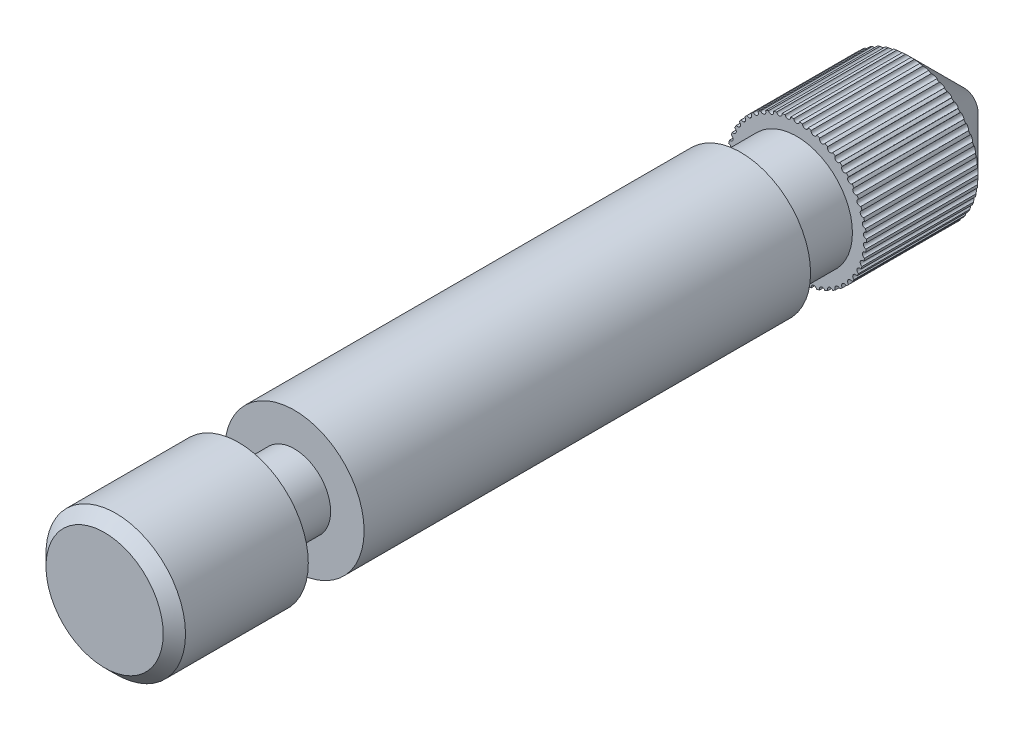
SolidWorks part; units mm, degrees
ref_plane "Front Plane" through (0, 0, 0) normal (0, 0, 1) x (1, 0, 0)
ref_plane "Top Plane" through (0, 0, 0) normal (0, 1, 0) x (1, 0, 0)
ref_plane "Right Plane" through (0, 0, 0) normal (1, 0, 0) x (0, 0, -1)
sketch "Sketch1" plane through (0, 0, 0) normal (0, 0, 1) x (1, 0, 0)
  circle A0 centre (0, 0) radius 1.25
  dimension "D1" = 2.5
extrude "Boss-Extrude1" add sketch "Sketch1" against normal blind 15.4
sketch "Sketch2" plane through (0, 0, 0) normal (1, 0, 0) x (0, 0, -1)
  line L0 (0, 0) -> (15.4, 0) construction
  line L1 (15.4, -1.25) -> (15.4, 1.25) construction
  line L2 (15.4, 1.25) -> (0, 1.25) construction
  line L3 (3.4, 1.25) -> (2.4, 1.25)
  line L6 (2.4, 1.25) -> (2.4, 0.65)
  line L7 (2.4, 0.65) -> (3.4, 0.65)
  line L8 (3.4, 1.25) -> (3.4, 0.65)
  dimension "D1" = 3.4
  dimension "D2" = 1
  dimension "D3" = 1.3
revolve "Cut-Revolve1" cut sketch "Sketch2" angle 360 about L0
sketch "Sketch3" plane through (0, 0, 0) normal (1, 0, 0) x (0, 0, -1)
  line L0 (15.4, 1.25) -> (3.4, 1.25) construction
  line L1 (12.4, 1.25) -> (11.4, 1.25)
  line L2 (12.4, 1.25) -> (12.4, 1)
  line L3 (12.4, 1) -> (11.4, 1)
  line L4 (11.4, 1.25) -> (11.4, 1)
  line L5 (0, 0) -> (15.4, 0) construction
  line L6 (0, 1.25) -> (0, -1.25) construction
  line L7 (15.4, -1.25) -> (15.4, 1.25) construction
  dimension "D1" = 2
  dimension "D2" = 3
  dimension "D3" = 1
revolve "Cut-Revolve2" cut sketch "Sketch3" angle 360 about L5
chamfer "Chamfer1" distance 1 angle 45 1 edges at (1.25, 0, -15.4)
chamfer "Chamfer2" distance 0.2 angle 45 1 edges at (1.25, 0, 0)
sketch "Sketch4" plane through (0, 0, -12.4) normal (0, 0, 1) x (1, 0, 0)
  line L0 (0, 0) -> (0, 1.25) construction
  circle A0 centre (0, 0) radius 1.25 construction
  circle A1 centre (0, 1.25) radius 0.05
  dimension "D1" = 0.1
extrude "Cut-Extrude2" cut sketch "Sketch4" against normal up to next contours A1
pattern_circular "CirPattern2" count 50 over 360 about axis through (0, 0, -15.4) along (0, 0, 1) of "Cut-Extrude2"
